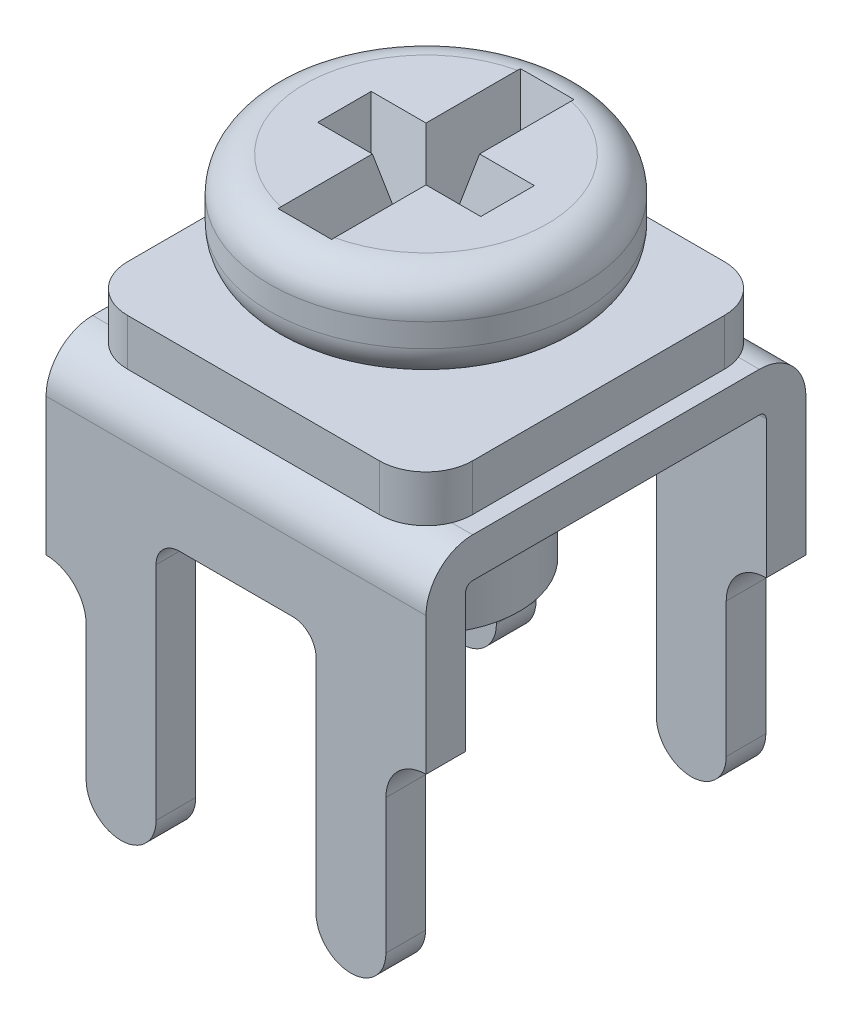
SolidWorks part; units mm, degrees
ref_plane "Front Plane" through (0, 0, 0) normal (0, 0, 1) x (1, 0, 0)
ref_plane "Top Plane" through (0, 0, 0) normal (0, 1, 0) x (1, 0, 0)
ref_plane "Right Plane" through (0, 0, 0) normal (1, 0, 0) x (0, 0, -1)
sketch "Sketch1" plane through (0, 0, 0) normal (1, 0, 0) x (0, 0, -1)
  line L0 (0, 39.8206) -> (0, -23.5518) construction
  line L1 (-3.075, 4.725) -> (3.075, 4.725)
  line L2 (4.075, 3.725) -> (4.075, -3.725)
  line L3 (-4.075, 3.725) -> (-4.075, -3.725)
  arc A0 (4.075, 3.725) -> (3.075, 4.725) centre (3.075, 3.725) ccw
  arc A1 (-4.075, 3.725) -> (-3.075, 4.725) centre (-3.075, 3.725) cw
  point P8 (4.075, 4.725)
  point P9 (4.075, 0)
  point P14 (0, 4.725)
  dimension "D3" = 1
  dimension "D1" = 8.15
  dimension "D2" = 8.45
extrude "Extrude-Thin1" add sketch "Sketch1" along normal mid plane 8.15 thin thin type one direction reverse wall 0.85
sketch "Sketch3" plane through (0, 0, 0) normal (0, 0, 1) x (1, 0, 0)
  line L0 (4.075, -3.725) -> (-4.075, -3.725) construction
  line L1 (-1.715, -3.725) -> (1.715, -3.725)
  line L2 (-1.715, -2.975) -> (-1.715, 1.775)
  line L3 (-1.215, 2.275) -> (1.215, 2.275)
  line L4 (1.715, -2.975) -> (1.715, 1.775)
  line L5 (-1.715, -3.725) -> (1.715, 2.275) construction
  line L6 (-1.715, 2.275) -> (1.715, -3.725) construction
  line L7 (3.215, -2.975) -> (3.215, -0.085)
  line L8 (4.075, 3.725) -> (4.075, -3.725) construction
  line L9 (4.075, 0.775) -> (4.075, -3.725)
  line L10 (4.075, -3.725) -> (3.215, -3.725)
  line L11 (0, 0) -> (0, -2.5996) construction
  line L12 (-4.075, -3.725) -> (-3.215, -3.725)
  line L13 (-4.075, 0.775) -> (-4.075, -3.725)
  line L14 (-3.215, -2.975) -> (-3.215, -0.085)
  line L15 (3.215, -3.725) -> (3.215, -2.975) construction
  line L16 (1.715, -3.725) -> (1.715, -2.975) construction
  line L17 (3.215, -3.725) -> (3.215, -3.9728)
  line L18 (3.215, -3.9728) -> (1.715, -3.9728)
  line L19 (1.715, -3.9728) -> (1.715, -3.725)
  line L20 (-3.215, -3.725) -> (-3.215, -3.9728)
  line L21 (-3.215, -3.9728) -> (-1.715, -3.9728)
  line L22 (-1.715, -3.9728) -> (-1.715, -3.725)
  line L23 (-3.215, -3.725) -> (-3.215, -2.975) construction
  line L24 (-1.715, -3.725) -> (-1.715, -2.975) construction
  arc A0 (1.215, 2.275) -> (1.715, 1.775) centre (1.215, 1.775) cw
  arc A1 (-1.715, 1.775) -> (-1.215, 2.275) centre (-1.215, 1.775) cw
  arc A2 (3.215, -0.085) -> (4.075, 0.775) centre (4.075, -0.085) cw
  arc A3 (-3.215, -0.085) -> (-4.075, 0.775) centre (-4.075, -0.085) ccw
  arc A4 (1.715, -2.975) -> (3.215, -2.975) centre (2.465, -2.975) ccw
  arc A5 (-1.715, -2.975) -> (-3.215, -2.975) centre (-2.465, -2.975) cw
  point P0 (0, -0.725)
  point P8 (0, -3.725)
  dimension "D3" = 0.5
  dimension "D4" = 1.5
  dimension "D1" = 6
  dimension "D2" = 3.43
  dimension "D5" = 4.5
extrude "Cut-Extrude1" cut sketch "Sketch3" against normal through all both and the other way through all
sketch "Sketch4" plane through (0, 4.725, 0) normal (0, 1, 0) x (1, 0, 0)
  line L1 (-2.7, -3.7) -> (2.7, -3.7)
  line L2 (-3.7, -2.7) -> (-3.7, 2.7)
  line L3 (-2.7, 3.7) -> (2.7, 3.7)
  line L4 (3.7, -2.7) -> (3.7, 2.7)
  line L5 (-3.7, -3.7) -> (3.7, 3.7) construction
  line L6 (-3.7, 3.7) -> (3.7, -3.7) construction
  arc A0 (2.7, 3.7) -> (3.7, 2.7) centre (2.7, 2.7) cw
  arc A1 (3.7, -2.7) -> (2.7, -3.7) centre (2.7, -2.7) cw
  arc A2 (-3.7, -2.7) -> (-2.7, -3.7) centre (-2.7, -2.7) ccw
  arc A3 (-3.7, 2.7) -> (-2.7, 3.7) centre (-2.7, 2.7) cw
  point P0 (0, 0)
  dimension "D2" = 1
  dimension "D1" = 7.4
extrude "Boss-Extrude1" add sketch "Sketch4" along normal blind 1
sketch "Sketch5" plane through (0, 5.725, 0) normal (0, 1, 0) x (1, 0, 0)
  circle A0 centre (0, 0) radius 2
  dimension "D1" = 4
extrude "Boss-Extrude2" add sketch "Sketch5" along normal blind 0.5 and the other way blind 5
sketch "Sketch6" plane through (0, 6.225, 0) normal (0, 1, 0) x (1, 0, 0)
  circle A0 centre (0, 0) radius 3.35
  dimension "D1" = 6.7
extrude "Boss-Extrude3" add sketch "Sketch6" along normal blind 2
fillet "Fillet1" radius 0.75 2 edges at (0, 6.225, 3.35) (0, 8.225, 3.35)
sketch "Sketch7" plane through (0, 8.225, 0) normal (0, 1, 0) x (1, 0, 0)
  line L0 (0, 2.6) -> (0, -2.6)
  line L1 (1.75, 0) -> (-1.75, 0)
  circle A0 centre (0, 0) radius 2.6 construction
  point P8 (0, 0)
extrude "Cut-Extrude-Thin1" cut sketch "Sketch7" against normal blind 2 draft 13 thin thin type mid plane wall 1.15
